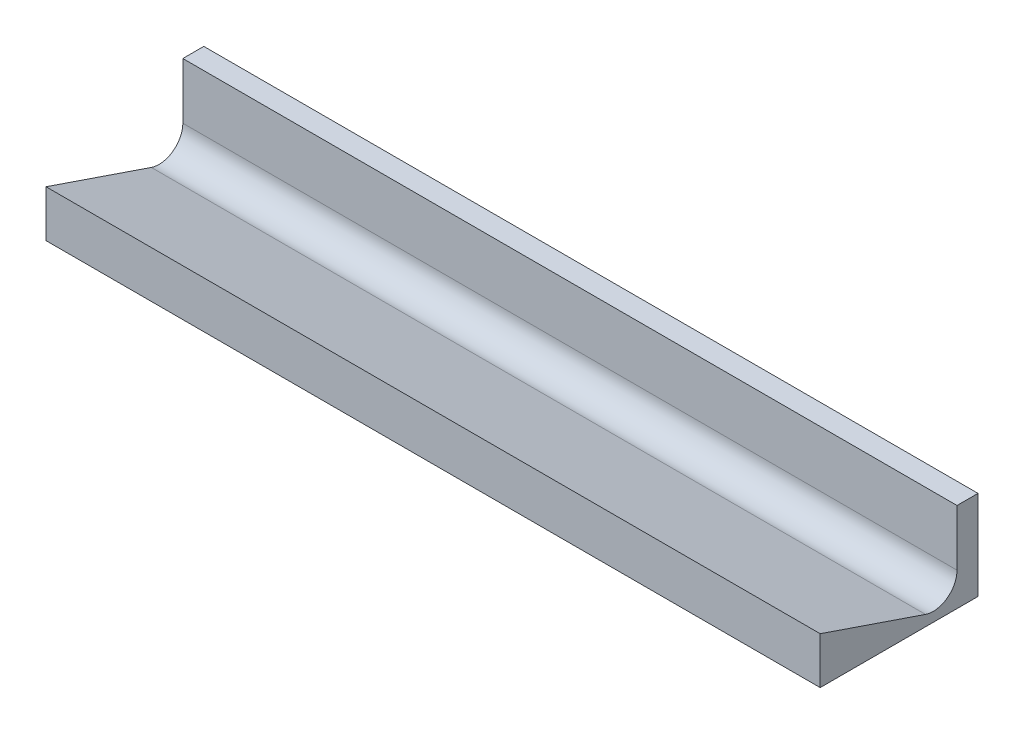
SolidWorks part; units mm, degrees
ref_plane "Front Plane" through (0, 0, 0) normal (0, 0, 1) x (1, 0, 0)
ref_plane "Top Plane" through (0, 0, 0) normal (0, 1, 0) x (1, 0, 0)
ref_plane "Right Plane" through (0, 0, 0) normal (1, 0, 0) x (0, 0, -1)
sketch "Sketch1" plane through (0, 0, 0) normal (0, 1, 0) x (1, 0, 0)
  line L1 (-65, -13.25) -> (65, -13.25)
  line L2 (-65, -13.25) -> (-65, 13.25)
  line L3 (-65, 13.25) -> (65, 13.25)
  line L4 (65, -13.25) -> (65, 13.25)
  line L5 (-65, -13.25) -> (65, 13.25) construction
  line L6 (-65, 13.25) -> (65, -13.25) construction
  point P0 (0, 0)
  dimension "D1" = 26.5
  dimension "D2" = 130
extrude "Boss-Extrude2" add sketch "Sketch1" along normal blind 15
sketch "Sketch2" plane through (-65, 0, 0) normal (-1, 0, 0) x (0, 0, 1)
  line L0 (13.25, 7.8389) -> (-4.4344, 1.8054)
  line L1 (13.25, 15) -> (13.25, 0) construction
  line L4 (-13.25, 0) -> (13.25, 0) construction
  line L5 (-9.726, 5.5911) -> (-9.726, 15)
  line L6 (-13.25, 15) -> (13.25, 15) construction
  arc A0 (-4.4344, 1.8054) -> (-9.726, 5.5911) centre (-5.726, 5.5911) cw
  point P11 (-9.726, 0)
  line M6 (13.25, 0) -> (13.25, 15)
  line M7 (13.25, 15) -> (-13.25, 15)
  dimension "D1" = 4
extrude "Cut-Extrude1" cut sketch "Sketch2" against normal through all and the other way through all contours A0 L0 L5 M6 M7 region at (-65, 9.4455, 0.6649)
sketch "Sketch4" plane through (0, 0, 0) normal (0, -1, 0) x (1, 0, 0)
  line L0 (0, -55) -> (0, 55) construction
  line L1 (-45, -1.25) -> (-40, -1.25)
  line L2 (-45, -1.25) -> (-45, -8.25)
  line L3 (-45, -8.25) -> (-40, -8.25)
  line L4 (-40, -1.25) -> (-40, -8.25)
  line L9 (65, -13.25) -> (-65, -13.25) construction
  line L10 (45, -8.25) -> (40, -8.25)
  line L11 (40, -1.25) -> (40, -8.25)
  line L12 (45, -1.25) -> (40, -1.25)
  line L13 (45, -1.25) -> (45, -8.25)
  dimension "D1" = 7
  dimension "D2" = 5
  dimension "D5" = 40
  dimension "D6" = 5
extrude "Boss-Extrude3" add sketch "Sketch4" along normal blind 8
ref_plane "Plane1" through (0, 0, -4.75) normal (0, 0, 1) x (1, 0, 0)
sketch "Sketch5" plane through (0, 0, -4.75) normal (0, 0, 1) x (1, 0, 0)
  line L1 (-45, -5) -> (-46, -5)
  line L2 (-46, -5) -> (-45, -8)
  line L3 (-40, -8) -> (-39, -5)
  line L4 (45, 0) -> (40, 0)
  line L5 (40, 0) -> (40, -8)
  line L6 (40, -8) -> (45, -8)
  line L7 (45, -8) -> (45, 0)
  line L9 (40, 0) -> (40, -8)
  line L10 (40, -8) -> (45, -8)
  line L11 (45, -8) -> (45, 0)
  line L12 (-40, 0) -> (-45, 0)
  line L13 (-45, 0) -> (-45, -8)
  line L14 (-45, -8) -> (-40, -8)
  line L15 (-40, -8) -> (-40, 0)
  line L17 (-45, 0) -> (-45, -8)
  line L18 (-45, -8) -> (-40, -8)
  line L19 (-40, -8) -> (-40, 0)
  line L20 (-39, -5) -> (-40, -5)
  line L21 (-43, 0) -> (-43, -8)
  line L22 (-42, -8) -> (-42, 0)
  line L23 (40, -5) -> (39, -5)
  line L24 (39, -5) -> (40, -8)
  line L25 (42, -8) -> (42, 0)
  line L26 (43, 0) -> (43, -8)
  line L27 (45, -5) -> (46, -5)
  line L28 (46, -5) -> (45, -8)
  line L32 (45, 0) -> (40, 0)
  line L33 (-40, 0) -> (-45, 0)
  dimension "D3" = 1
  dimension "D4" = 1
  dimension "D5" = 2
  dimension "D6" = 2
  dimension "D8" = 3
  dimension "D9" = 1
  dimension "D10" = 1
  dimension "D11" = 3
  dimension "D12" = 2
  dimension "D13" = 2
  dimension "D1" = 0
  dimension "D2" = 0
extrude "Boss-Extrude4" add sketch "Sketch5" along normal mid plane 7 contours L17 L1 L2 | L3 L20 L19 | L28 L27 L11 | L23 L24 L9 region at (-45.3333, -6, -4.75) region at (-39.6667, -6, -4.75) region at (45.3333, -6, -4.75) region at (39.6667, -6, -4.75)
extrude "Cut-Extrude2" cut sketch "Sketch5<3>" against normal mid plane 7 contours L18 L22 L33 L21 | L26 L32 L25 L10 region at (-42.5, -4, -4.75) region at (42.5, -4, -4.75)
sketch "Sketch5<3>" plane through (0, 0, -4.75) normal (0, 0, 1) x (1, 0, 0) same geometry as "Sketch5"
